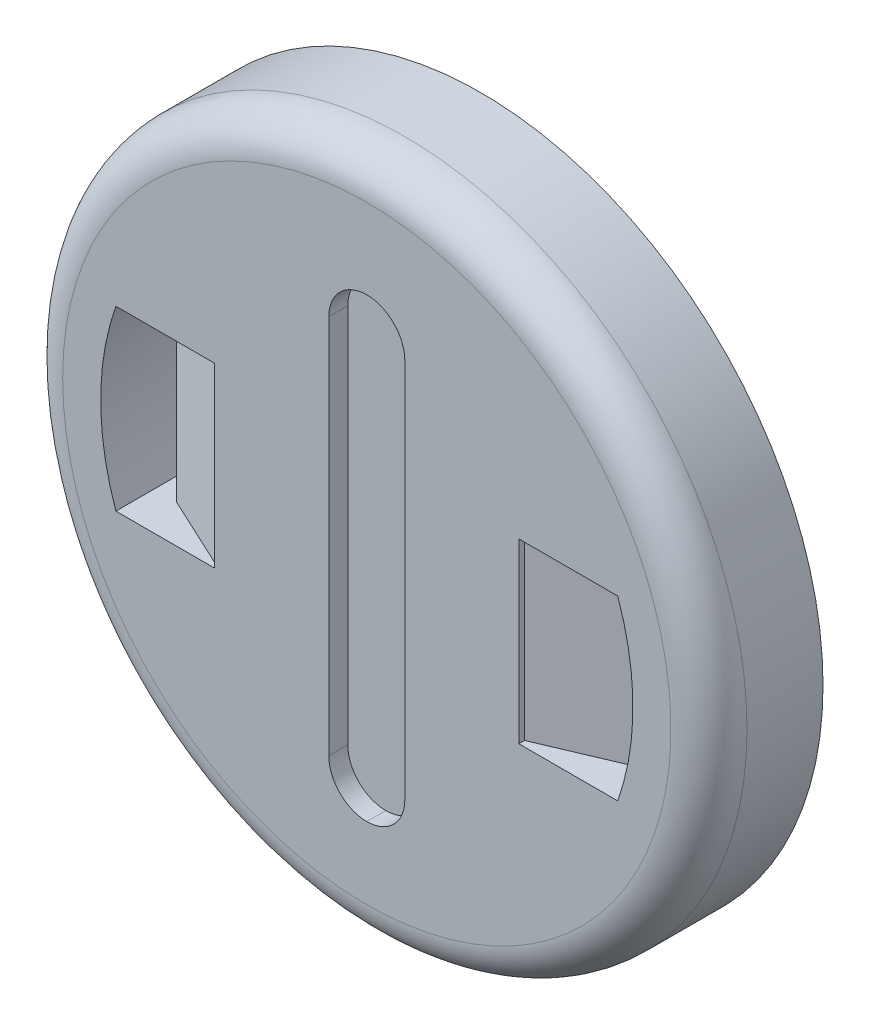
SolidWorks part; units mm, degrees
material "PUR"
ref_plane "Front Plane" through (0, 0, 0) normal (0, 0, 1) x (1, 0, 0)
ref_plane "Top Plane" through (0, 0, 0) normal (0, 1, 0) x (1, 0, 0)
ref_plane "Right Plane" through (0, 0, 0) normal (1, 0, 0) x (0, 0, -1)
sketch "草图1" plane through (0, 0, 12) normal (0, 0, -1) x (-1, 0, 0)
  circle A0 centre (0, 0) radius 9
extrude "凸台-拉伸1" add sketch "草图1" against normal blind 3
fillet "圆角1" radius 1 1 edges at (-9, 0, 15)
sketch "草图3" plane through (0, 0, 15) normal (0, 0, 1) x (1, 0, 0)
  line L0 (0, 8) -> (0, -8) construction
  line L1 (-1, 5.8946) -> (1, 5.8946)
  line L2 (-1, 5.8946) -> (-1, -6.1054)
  line L3 (-1, -6.1054) -> (1, -6.1054)
  line L4 (1, 5.8946) -> (1, -6.1054)
  point P5 (0, 5.8946)
extrude "切除-拉伸1" cut sketch "草图3" against normal blind 0.5
fillet "圆角2" radius 1 4 edges at (1, -6.1054, 14.75) (-1, -6.1054, 14.75) (1, 5.8946, 14.75) (-1, 5.8946, 14.75)
sketch "草图4" plane through (0, 0, 15) normal (0, 0, 1) x (1, 0, 0)
  line L1 (-6.5997, 2.3333) -> (-4, 2.3333)
  line L2 (-6.5997, -2.3333) -> (-4, -2.3333)
  line L3 (4, -2.3333) -> (6.5997, -2.3333)
  line L5 (4, 2.3333) -> (6.5997, 2.3333)
  line L6 (-4, 2.3333) -> (-4, -2.3333)
  line L8 (4, 2.3333) -> (4, -2.3333)
  arc A1 (-6.5997, 2.3333) -> (-6.5997, -2.3333) centre (0, 0) ccw
  arc A4 (6.5997, -2.3333) -> (6.5997, 2.3333) centre (0, 0) ccw
extrude "切除-拉伸2" cut sketch "草图4" against normal blind 1
chamfer "倒角2" distance 2 angle 25 1 edges at (-4, 0, 14) first distance on face at (-5.3999, 0, 14)
chamfer "倒角5" distance 2 angle 23 1 edges at (4, 0, 14) first distance on face at (5.3999, 0, 14)
sketch "草图6" plane through (0, 0, 14) normal (0, 0, 1) x (1, 0, 0)
  line L0 (-6.5997, -2.3333) -> (-6, -2.3333) construction
  line L1 (-6, -2.3333) -> (-6, 2.3333) construction
  line L2 (-6, 2.3333) -> (-6.5997, 2.3333) construction
  line L3 (6.5997, 2.3333) -> (6, 2.3333) construction
  line L4 (6, 2.3333) -> (6, -2.3333) construction
  line L5 (6, -2.3333) -> (6.5997, -2.3333) construction
  line L6 (-6.5997, -2.3333) -> (-6, -2.3333)
  line L7 (-6, -2.3333) -> (-6, 2.3333)
  line L8 (-6, 2.3333) -> (-6.5997, 2.3333)
  line L9 (6.5997, 2.3333) -> (6, 2.3333)
  line L10 (6, 2.3333) -> (6, -2.3333)
  line L11 (6, -2.3333) -> (6.5997, -2.3333)
  arc A0 (-6.5997, 2.3333) -> (-6.5997, -2.3333) centre (0, 0) ccw construction
  arc A1 (6.5997, -2.3333) -> (6.5997, 2.3333) centre (0, 0) ccw construction
  arc A2 (-6.5997, 2.3333) -> (-6.5997, -2.3333) centre (0, 0) ccw
  arc A3 (6.5997, -2.3333) -> (6.5997, 2.3333) centre (0, 0) ccw
extrude "切除-拉伸3" cut sketch "草图6" against normal blind 8
sketch "草图7" plane through (0, 0, 12) normal (0, 0, -1) x (-1, 0, 0)
  circle A0 centre (0, 0) radius 7
extrude "切除-拉伸4" cut sketch "草图7" against normal blind 2
sketch "草图8" plane through (0, 0, 14) normal (0, 0, -1) x (-1, 0, 0)
  line L6 (-6.5997, 2.3333) -> (-6, 2.3333)
  line L7 (-6, 2.3333) -> (-6, -2.3333)
  line L8 (-6, -2.3333) -> (-6.5997, -2.3333)
  line L9 (6.5997, -2.3333) -> (6, -2.3333)
  line L10 (6, -2.3333) -> (6, 2.3333)
  line L11 (6, 2.3333) -> (6.5997, 2.3333)
  line L12 (-6.5997, 2.3333) -> (-6, 2.3333)
  line L13 (-6, 2.3333) -> (-6, -2.3333)
  line L14 (-6, -2.3333) -> (-6.5997, -2.3333)
  line L15 (6.5997, -2.3333) -> (6, -2.3333)
  line L16 (6, -2.3333) -> (6, 2.3333)
  line L17 (6, 2.3333) -> (6.5997, 2.3333)
  arc A2 (-6.5997, -2.3333) -> (6.5997, -2.3333) centre (0, 0) ccw
  arc A3 (6.5997, 2.3333) -> (-6.5997, 2.3333) centre (0, 0) ccw
  arc A4 (-6.5997, -2.3333) -> (6.5997, -2.3333) centre (0, 0) ccw
  arc A5 (6.5997, 2.3333) -> (-6.5997, 2.3333) centre (0, 0) ccw
  dimension "D1" = 0
extrude "凸台-拉伸2" add sketch "草图8" along normal up to surface (2 mm away) up to face at (-7, 0, 12)
sketch "草图9" plane through (0, 0, 12) normal (0, 0, -1) x (-1, 0, 0)
  circle A0 centre (0, 0) radius 8
extrude "切除-拉伸5" cut sketch "草图9" against normal blind 0.5
